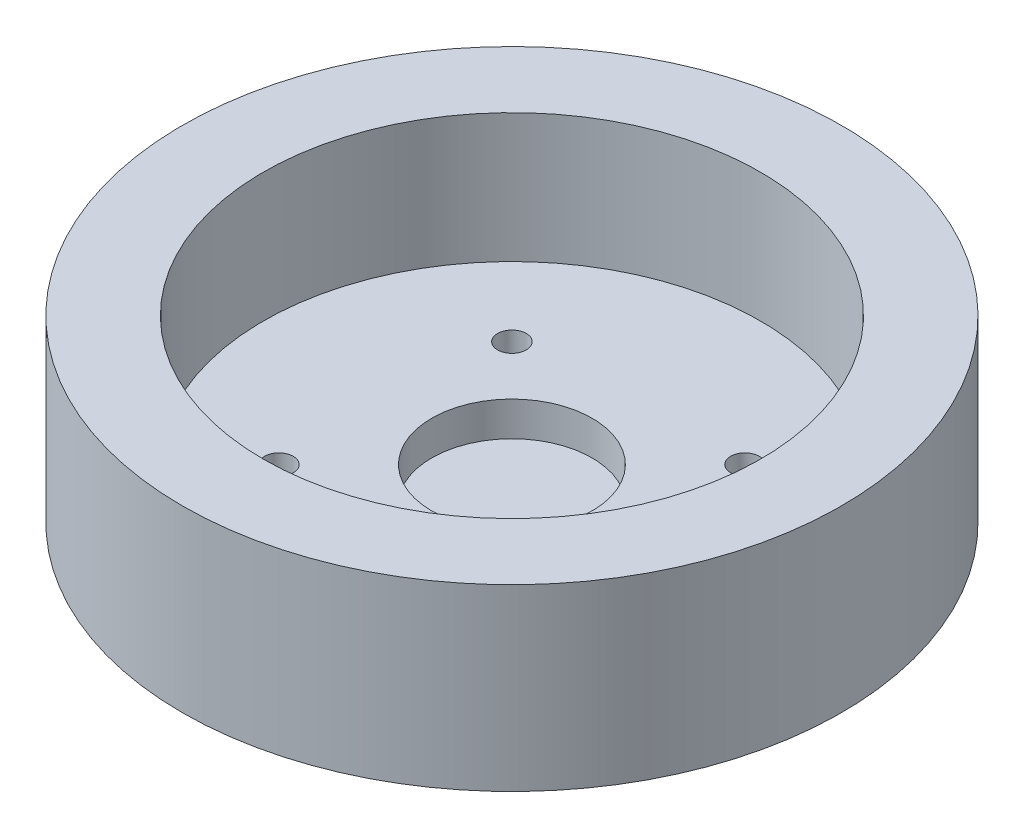
SolidWorks part; units mm, degrees
ref_plane "前视基准面" through (0, 0, 0) normal (0, 0, 1) x (1, 0, 0)
ref_plane "上视基准面" through (0, 0, 0) normal (0, 1, 0) x (1, 0, 0)
ref_plane "右视基准面" through (0, 0, 0) normal (1, 0, 0) x (0, 0, -1)
sketch "草图1" plane through (0, 0, 0) normal (0, 1, 0) x (1, 0, 0)
  circle A0 centre (0, 0) radius 16.35
  circle A1 centre (0, 0) radius 5.6
  circle A2 centre (0, 0) radius 15 construction
  circle A3 centre (0, 0) radius 23
  circle A4 centre (0, 0) radius 17.35
  dimension "D1" = 32.7
  dimension "D2" = 11.2
  dimension "D3" = 30
  dimension "D4" = 46
  dimension "D5" = 34.7
extrude "凸台-拉伸1" add sketch "草图1" along normal blind 3.5 contours A1 | A4 region at (0, 0, 0)
sketch "草图3" plane through (0, 0, 0) normal (0, 1, 0) x (1, 0, 0)
  circle A0 centre (0, 0) radius 23 construction
  circle A1 centre (0, 0) radius 23
  circle A2 centre (0, 0) radius 17.35 construction
  circle A3 centre (0, 0) radius 17.35
extrude "凸台-拉伸3" add sketch "草图3" along normal blind 12.5
sketch "草图4" plane through (0, 0, 0) normal (0, 1, 0) x (1, 0, 0)
  circle A0 centre (0, 0) radius 5.6 construction
  circle A1 centre (0, 0) radius 5.6
extrude "凸台-拉伸4" add sketch "草图4" along normal blind 1.1
sketch "草图6" plane through (0, 0, 0) normal (0, 1, 0) x (1, 0, 0)
  line L0 (-23.1107, 23.1107) -> (0, 0) construction
  line L1 (0, 0) -> (22.5537, 22.5537) construction
  circle A0 centre (0, 0) radius 16.35 construction
  circle A1 centre (0, 0) radius 16.35 construction
  circle A2 centre (0, 0) radius 17.35 construction
  circle A3 centre (0, 0) radius 17.35 construction
  circle A4 centre (8.1317, 8.1317) radius 1
  circle A5 centre (7.4246, -7.4246) radius 1
  circle A6 centre (-8.1317, -8.1317) radius 1
  circle A7 centre (-7.4246, 7.4246) radius 1
  circle A8 centre (0, 0) radius 5.6 construction
  circle A9 centre (0, 0) radius 5.6 construction
  dimension "D1" = 32.7
  dimension "D2" = 34.7
  dimension "D3" = 2
  dimension "D4" = 2
  dimension "D5" = 2
  dimension "D6" = 2
  dimension "D7" = 11.2
  dimension "D8" = 10.5
  dimension "D9" = 10.5
  dimension "D10" = 11.5
  dimension "D11" = 11.5
extrude "切除-拉伸3" cut sketch "草图6" against normal mid plane 10
sketch "草图8" plane through (0, 0, 0) normal (0, -1, 0) x (1, 0, 0)
  circle A0 centre (-8.1317, 8.1317) radius 1 construction
  circle A1 centre (-8.1317, 8.1317) radius 1 construction
  circle A2 centre (-8.1317, 8.1317) radius 1.91
  circle A3 centre (7.4246, 7.4246) radius 1.91
  circle A4 centre (-7.4246, -7.4246) radius 1.91
  circle A5 centre (8.1317, -8.1317) radius 1.91
  dimension "D1" = 3.82
  dimension "D2" = 3.82
  dimension "D3" = 3.82
  dimension "D4" = 3.82
extrude "切除-拉伸4" cut sketch "草图8" against normal blind 1.9
